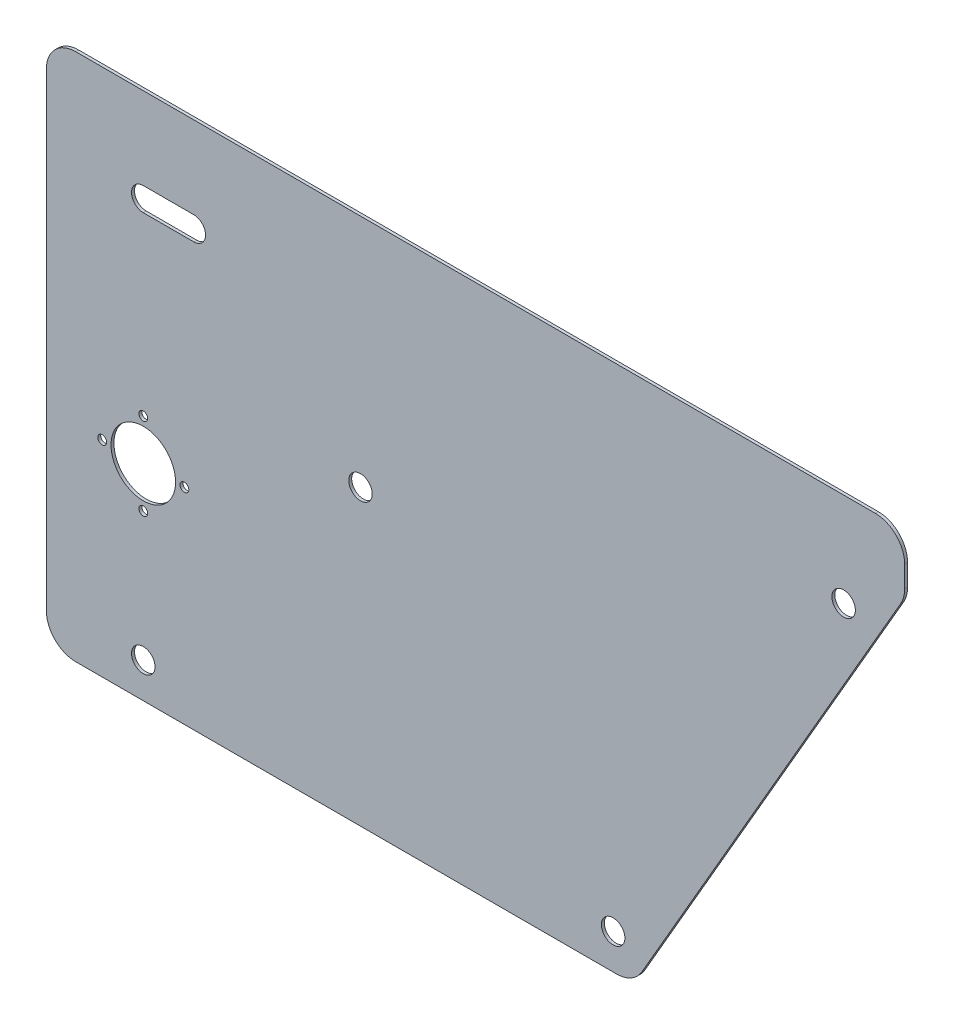
SolidWorks part; units mm, degrees
ref_plane "Front Plane" through (0, 0, 0) normal (0, 0, 1) x (1, 0, 0)
ref_plane "Top Plane" through (0, 0, 0) normal (0, 1, 0) x (1, 0, 0)
ref_plane "Right Plane" through (0, 0, 0) normal (1, 0, 0) x (0, 0, -1)
sketch "Sketch1" plane through (0, 0, 0) normal (0, 0, 1) x (1, 0, 0)
  line L0 (100, 80) -> (192.376, 80)
  line L1 (-100, -80) -> (100, -80)
  line L2 (-100, -80) -> (-100, 80)
  line L3 (-100, 80) -> (100, 80)
  line L4 (100, -80) -> (100, 80)
  line L5 (-100, -80) -> (100, 80) construction
  line L6 (-100, 80) -> (100, -80) construction
  line L7 (192.376, 80) -> (100, -80)
  line L8 (100, 80) -> (100, -80)
  line L10 (-100, 80) -> (192.376, 80)
  line L11 (-100, 80) -> (-100, 100)
  line L12 (-100, 100) -> (192.376, 100)
  line L13 (192.376, 80) -> (192.376, 100)
  point P0 (0, 0)
  dimension "D1" = 160
  dimension "D2" = 200
  dimension "D3" = 30
  dimension "D4" = 20
extrude "Boss-Extrude1" add sketch "Sketch1" along normal blind 1 contours L1 L4 L3 L2 | L7 L0 L4 | L11 L10 L13 L12 region at (0, 0, 0) region at (130.792, 26.6667, 0)
fillet "Fillet1" radius 10 5 edges at (100, -80, 0.5) (-100, -80, 0.5) (192.376, 100, 0.5) (-100, 100, 0.5) (192.376, 80, 0.5)
sketch "Sketch2" plane through (0, 0, 1) normal (0, 0, 1) x (1, 0, 0)
  line L0 (-90, -80) -> (94.2265, -80) construction
  line L1 (191.0363, 77.6795) -> (102.8868, -75) construction
  line L3 (-90, 100) -> (182.376, 100) construction
  line L4 (-67, 68) -> (-49.7837, 68) construction
  line L7 (-100, -70) -> (-100, 90) construction
  line L9 (-67, 72) -> (-49.7837, 72)
  line L10 (-67, 64) -> (-49.7837, 64)
  circle A0 centre (93.0718, -68) radius 4
  circle A1 centre (171.5914, 68) radius 4
  circle A2 centre (-67, -10) radius 11
  circle A3 centre (-67, -68) radius 4
  circle A4 centre (-53, -10) radius 1.5
  circle A5 centre (-67, 4) radius 1.5
  circle A6 centre (-81, -10) radius 1.5
  circle A7 centre (-67, -24) radius 1.5
  circle A10 centre (6.9988, 20) radius 4
  arc A11 (-67, 72) -> (-67, 64) centre (-67, 68) ccw
  arc A12 (-49.7837, 64) -> (-49.7837, 72) centre (-49.7837, 68) ccw
  point P12 (-58.3919, 68)
  dimension "D3" = 8
  dimension "D4" = 8
  dimension "D9" = 22
  dimension "D10" = 8
  dimension "D12" = 3
  dimension "D13" = 3
  dimension "D14" = 3
  dimension "D15" = 3
  dimension "D16" = 14
  dimension "D20" = 4
  dimension "D22" = 8
  dimension "D1" = 12
  dimension "D2" = 12
  dimension "D5" = 32
  dimension "D6" = 12
  dimension "D7" = 33
  dimension "D8" = 70
  dimension "D11" = 12
  dimension "D17" = 14
  dimension "D18" = 14
  dimension "D19" = 14
  dimension "D21" = 80
extrude "Cut-Extrude1" cut sketch "Sketch2" against normal blind 3
